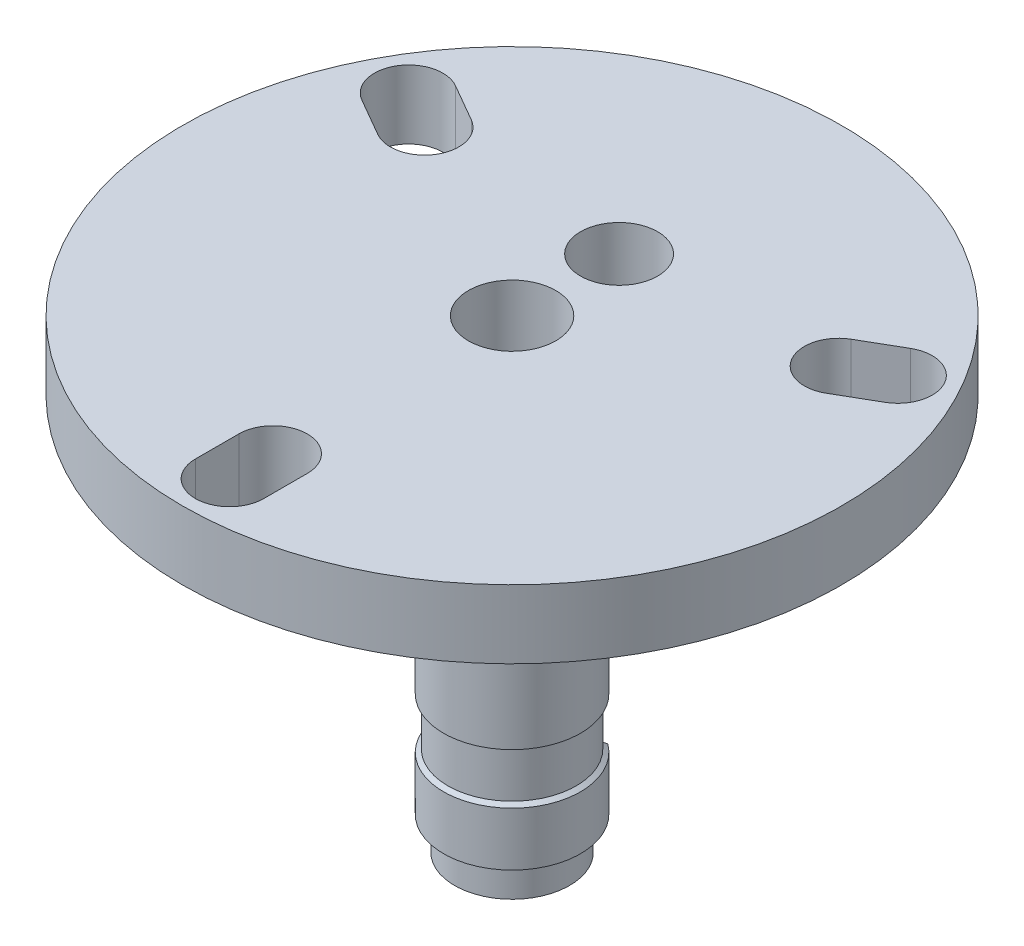
SolidWorks part; units mm, degrees
ref_plane "Front Plane" through (0, 0, 0) normal (0, 0, 1) x (1, 0, 0)
ref_plane "Top Plane" through (0, 0, 0) normal (0, 1, 0) x (1, 0, 0)
ref_plane "Right Plane" through (0, 0, 0) normal (1, 0, 0) x (0, 0, -1)
sketch "Sketch1" plane through (0, 0, 0) normal (0, 1, 0) x (1, 0, 0)
  line L0 (-2, -16.5) -> (-2, -13.96)
  line L1 (2, -16.5) -> (2, -13.96)
  line L2 (0, -16.5) -> (0, 0) construction
  line L3 (0, 0) -> (38.1669, 22.0357) construction
  line L4 (0, 0) -> (-43.0695, 24.8662) construction
  line L5 (-11.0897, 8.7121) -> (-13.0897, 5.2479) construction
  line L6 (-13.2894, 9.9821) -> (-15.2894, 6.5179) construction
  line L7 (11.0897, 8.7121) -> (13.0897, 5.2479) construction
  line L8 (13.2894, 9.9821) -> (15.2894, 6.5179) construction
  line L9 (13.0897, 5.2479) -> (15.2894, 6.5179)
  line L10 (13.2894, 9.9821) -> (11.0897, 8.7121)
  line L11 (-15.2894, 6.5179) -> (-13.0897, 5.2479)
  line L12 (-13.2894, 9.9821) -> (-11.0897, 8.7121)
  circle A0 centre (0, 0) radius 16.5
  circle A1 centre (0, 0) radius 19.25
  arc A2 (-1.9963, -16.3788) -> (1.9963, -16.3788) centre (0, -16.5) ccw
  arc A3 (2, -13.96) -> (-2, -13.96) centre (0, -13.96) ccw
  circle A4 centre (0, 0) radius 4
  arc A5 (15.1826, 6.4605) -> (13.1863, 9.9183) centre (14.2894, 8.25) ccw
  arc A6 (-13.1863, 9.9183) -> (-15.1826, 6.4605) centre (-14.2894, 8.25) ccw
  arc A7 (-13.0897, 5.2479) -> (-11.095, 8.7151) centre (-12.0897, 6.98) ccw
  arc A8 (11.0897, 8.7121) -> (13.0897, 5.2479) centre (12.0897, 6.98) ccw
  dimension "D1" = 38.5
  dimension "D2" = 33
  dimension "D3" = 4
  dimension "D5" = 8
  dimension "D8" = 4
  dimension "D9" = 4
  dimension "D10" = 4
  dimension "D11" = 4
  dimension "D4" = 2.54
  dimension "D6" = 120
  dimension "D7" = 120
  dimension "D12" = 2.54
  dimension "D15" = 2.54
extrude "Boss-Extrude1" add sketch "Sketch1" against normal blind 4 contours A1 A6 L12 A0 L10 A5 L9 L1 A2 L0 L11 | A8 L10 A0 L12 A7 L11 L0 A3 L1 L9 A4 region at (-13.886, 0, 8.0171) region at (-18.7055, 0, 0)
extrude "Boss-Extrude2" add sketch "Sketch1<4>" against normal offset from surface (27.15 mm away) 27.15 contours A4 region at (0, 0, 0) up to face at (-13.1896, 0, -7.615)
sketch "Sketch1<4>" plane through (0, 0, 0) normal (0, 1, 0) x (1, 0, 0) same geometry as "Sketch1"
sketch "Sketch2" plane through (0, 0, 0) normal (1, 0, 0) x (0, 0, -1)
  line L0 (0, 0) -> (0, -27.15) construction
  line L2 (0.8, -27.15) -> (0.8, -25.15)
  line L3 (1, 0) -> (0.8, -25.15)
  line L4 (-4, -27.15) -> (4, -27.15) construction
  line L6 (19.25, 0) -> (-19.25, 0) construction
  line L7 (0, 0) -> (1, 0)
  line L8 (0, -27.15) -> (0.8, -27.15)
  line L9 (0, 0) -> (0, -27.15)
  line L10 (0, -27.15) -> (0.8, -27.15)
  dimension "D1" = 2
  dimension "D2" = 1
  dimension "D3" = 0.8
revolve "Cut-Revolve4" cut sketch "Sketch2" angle 360 about L0 region at (0, -13.0362, -0.4484)
ref_axis "Axis1" through (0, 0, 0) along (0, -1, 0)
sketch "Sketch5" plane through (0, 0, 0) normal (0, 0, 1) x (1, 0, 0)
  line L0 (0, 0) -> (0, -7) construction
  line L1 (0, -7) -> (-2.55, -5.5278)
  line L2 (-2.55, -5.5278) -> (-2.55, 0)
  line L3 (-2.55, 0) -> (0, 0)
  line L4 (1, 0) -> (-1, 0) construction
  line L5 (0, 0) -> (0, -7) construction
  line L6 (0, 0) -> (0, -7)
  dimension "D1" = 7
  dimension "D2" = 60
  dimension "D3" = 2.55
  dimension "D4" = 5.5278
revolve "Cut-Revolve8" cut sketch "Sketch5" angle 360 about axis through (0, 0, 0) along (0, -1, 0)
sketch "Sketch6" plane through (0, -27.15, 0) normal (0, -1, 0) x (1, 0, 0)
  circle A0 centre (0, 0) radius 4
  circle A3 centre (0, 0) radius 4 construction
  circle A4 centre (0, 0) radius 3.356
  circle A5 centre (0, 0) radius 3.356
  dimension "D1" = 0.644
extrude "Cut-Extrude1" cut sketch "Sketch6" against normal blind 1.932
sketch "Sketch7" plane through (0, -4, 0) normal (0, -1, 0) x (1, 0, 0)
  line L0 (0, 0) -> (0, -19.25) construction
  circle A0 centre (0, -6.25) radius 2.25
  circle A1 centre (0, 0) radius 4 construction
  circle A2 centre (0, 0) radius 19.25 construction
  dimension "D1" = 4.5
extrude "Cut-Extrude2" cut sketch "Sketch7" against normal through all
ref_plane "Plane1" through (0, -23, 0) normal (0, 1, 0) x (1, 0, 0)
sketch "Sketch8" plane through (0, -23, 0) normal (0, 1, 0) x (1, 0, 0)
  line L0 (0, 0) -> (0, 6.5) construction
  circle A0 centre (0, 4) radius 2.5
  circle A1 centre (0, 0) radius 4 construction
  dimension "D1" = 5
extrude "Cut-Extrude3" cut sketch "Sketch8" along normal blind 5
chamfer "Chamfer1" distance 2 angle 20 1 edges at (0, -18, -4) first distance on face at (0, -20.5, -3.6094)
sketch "Sketch9" plane through (0, 0, 0) normal (1, 0, 0) x (0, 0, -1)
  line L0 (4, -23) -> (3.2187, -23) construction
  line L1 (-4, -19.125) -> (-3.75, -19.125)
  line L2 (-4, -19.125) -> (-4, -21.875)
  line L3 (-4, -21.875) -> (-3.75, -21.875)
  line L4 (-3.75, -19.125) -> (-3.75, -21.875)
  line L5 (-4, -4) -> (-4, -25.218) construction
  line L6 (0, -27.15) -> (0, 0) construction
  line L7 (-0.8, -27.15) -> (0.8, -27.15) construction
  line L8 (2.55, 0) -> (-2.55, 0) construction
  point P4 (-4, -20.5)
  dimension "D1" = 2.75
  dimension "D2" = 0.25
  dimension "D3" = 2.5
revolve "Cut-Revolve9" cut sketch "Sketch9" angle 360 about L6
chamfer "Chamfer3" distance 0.3 angle 35 1 edges at (0, -21.875, 4) first distance on face at (0, -21.875, 0.3893)
